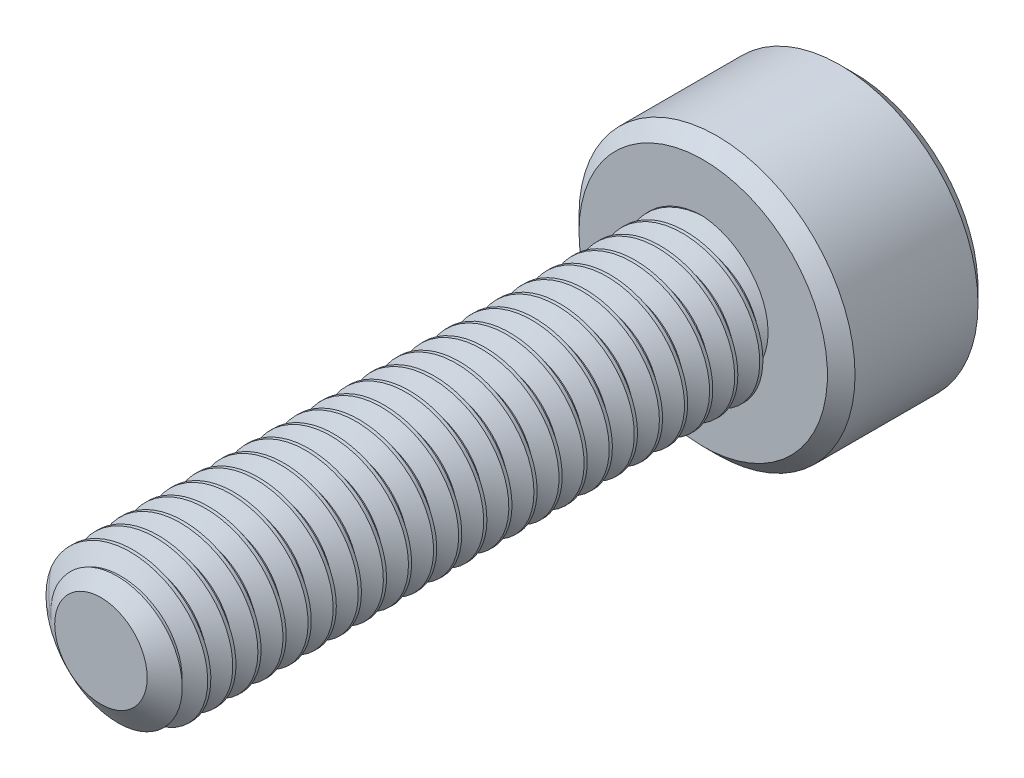
SolidWorks part; units mm, degrees
ref_plane "Front Plane" through (0, 0, 0) normal (0, 0, 1) x (1, 0, 0)
ref_plane "Top Plane" through (0, 0, 0) normal (0, 1, 0) x (1, 0, 0)
ref_plane "Right Plane" through (0, 0, 0) normal (1, 0, 0) x (0, 0, -1)
sketch "Sketch1" plane through (0, 0, 0) normal (0, 0, 1) x (1, 0, 0)
  circle A0 centre (0, 0) radius 1.5
  dimension "OD" = 3
extrude "Extrude1" add sketch "Sketch1" against normal blind 12
sketch "Sketch2" plane through (0, 0, 0) normal (0, 0, 1) x (1, 0, 0)
  circle A0 centre (0, 0) radius 1.5 construction
  circle A1 centre (0, 0) radius 1.5
curve "Helix/Spiral1" pitch 0.5 height 12.5 radius 1.5 centre (0, 0, 0) axis (0, 0, -1) start towards (0, 1, 0) parameters "pitch"=0.5
sketch "Sketch3" plane through (0, 0, 0) normal (1, 0, 0) x (0, 0, -1)
  line L0 (-0.4375, 1.5) -> (-0.25, 1.1752)
  line L1 (-0.25, 1.1752) -> (-0.1875, 1.1752)
  line L2 (-0.1875, 1.1752) -> (0, 1.5)
  line L3 (-0.4375, 1.5) -> (0, 1.5)
  line L4 (-0.2187, 1.5) -> (-0.2187, 1.1752) construction
  line L5 (-0.3437, 1.3376) -> (-0.0937, 1.3376) construction
  line L6 (0, 1.5) -> (0, -1.5) construction
  dimension "D1" = 0.0625
  dimension "D2" = 0.25
  dimension "D3" = 60
sweep "Cut-Sweep1" cut profiles "Sketch3" path "Helix/Spiral1"
sketch "Sketch4" plane through (0, 0, 0) normal (1, 0, 0) x (0, 0, -1)
  line L0 (0.4053, 1.5) -> (0, 0.9212)
  line L1 (0, 0.9212) -> (0, 1.5)
  line L2 (0.4053, 1.5) -> (0, 1.5)
  line L3 (-0.4375, 1.5) -> (0, 1.5) construction
  line L4 (0, 0) -> (7.0209, 0) construction
  dimension "D1" = 55
  dimension "D2" = 0.254
revolve "Cut-Revolve1" cut sketch "Sketch4" angle 360 about L4
sketch "Sketch5" plane through (0, 0, 0) normal (1, 0, 0) x (0, 0, -1)
  line L0 (12, -1.1822) -> (12, 1.0703) construction
  line L1 (12, 1.627) -> (87.4327, 1.627)
  line L2 (12, 1.627) -> (12, 0)
  line L3 (12, 0) -> (87.3125, 0)
  line L4 (87.3125, 1.2968) -> (87.3125, 0)
  line L5 (87.4327, 1.627) -> (87.3125, 1.2968)
  line L6 (0, 0) -> (9.9695, 0) construction
  point P3 (87.3125, 1.627)
  point P10 (87.3125, 1.627)
  dimension "D1" = 0.3302
  dimension "Thread min" = 87.3125
  dimension "D2" = 0.127
  dimension "D3" = 20
revolve "partially thread" [suppressed] add sketch "Sketch5" angle 360 about L6
sketch "Sketch6" plane through (0, 0, -12) normal (0, 0, -1) x (-1, 0, 0)
  circle A0 centre (0, 0) radius 2.75
  dimension "head dia" = 5.5
extrude "Extrude2" add sketch "Sketch6" along normal blind 3
sketch "Sketch7" plane through (0, 0, -15) normal (0, 0, -1) x (-1, 0, 0)
  line L1 (0, 1.4434) -> (-1.25, 0.7217)
  line L2 (-1.25, 0.7217) -> (-1.25, -0.7217)
  line L3 (-1.25, -0.7217) -> (0, -1.4434)
  line L4 (0, -1.4434) -> (1.25, -0.7217)
  line L5 (1.25, -0.7217) -> (1.25, 0.7217)
  line L6 (1.25, 0.7217) -> (0, 1.4434)
  circle A0 centre (0, 0) radius 1.25 construction
  dimension "hex dia" = 2.5
extrude "Cut-Extrude1" cut sketch "Sketch7" against normal blind 1.875
sketch "Sketch8" plane through (0, 0, -15) normal (0, 0, -1) x (-1, 0, 0)
  circle A0 centre (0, 0) radius 1.4434
extrude "Cut-Extrude2" cut sketch "Sketch8" against normal through all draft 45
chamfer "Chamfer1" distance 0.275 angle 45 2 edges at (-2.75, 0, -15) (-2.75, 0, -12)
sketch "Sketch9" plane through (0, 0, 0) normal (1, 0, 0) x (0, 0, -1)
  line L0 (0, 1.5) -> (0, -1.5) construction
  line L1 (2.75, 1.5) -> (2.75, -1.5) construction
  dimension "D1" = 2.75
equation "\"D3@Helix/Spiral1\" = \"screw length@Extrude1\"+\"pitch@Helix/Spiral1\""
equation "\"D1@Sketch3\" = \"pitch@Helix/Spiral1\"*.125"
equation "\"D2@Sketch3\" = \"pitch@Helix/Spiral1\"*.5"
equation "\"D1@Cut-Extrude1\" = \"hex dia@Sketch7\"*.75"
equation "\"D1@Chamfer1\" = \"head dia@Sketch6\"*.05"
equation "\"D1@Sketch9\" = \"pitch@Helix/Spiral1\"*5.5"
